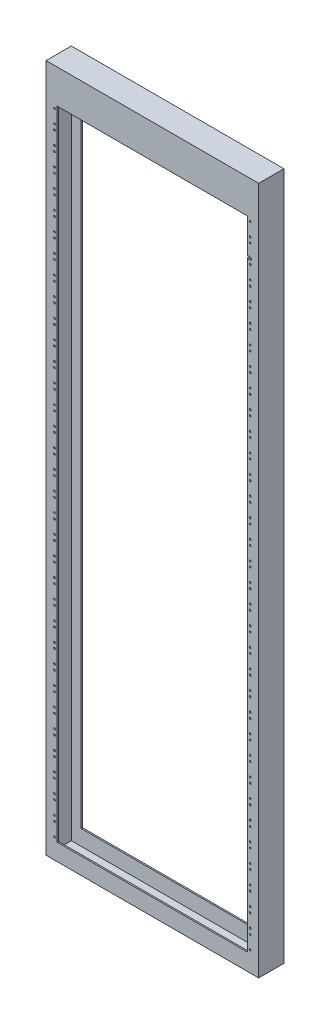
SolidWorks part; units mm, degrees
ref_plane "Front Plane" through (0, 0, 0) normal (0, 0, 1) x (1, 0, 0)
ref_plane "Top Plane" through (0, 0, 0) normal (0, 1, 0) x (1, 0, 0)
ref_plane "Right Plane" through (0, 0, 0) normal (1, 0, 0) x (0, 0, -1)
sketch "Sketch1" plane through (0, 0, 0) normal (0, 0, 1) x (1, 0, 0)
  line L0 (-26.5, -40) -> (-26.5, 1594.9)
  line L1 (0, 0) -> (452, 0)
  line L2 (0, 0) -> (0, 1514.4)
  line L3 (0, 1514.4) -> (452, 1514.4)
  line L4 (452, 0) -> (452, 1514.4)
  line L5 (-26.5, 1594.9) -> (478.5, 1594.9)
  line L6 (478.5, -40) -> (478.5, 1594.9)
  line L7 (-26.5, -40) -> (478.5, -40)
  dimension "D2" = 452
  dimension "D3" = 1634.9
  dimension "D4" = 505
  dimension "D1" = 1514.4
  dimension "D5" = 80.5
  dimension "D6" = 26.5
extrude "Boss-Extrude1" add sketch "Sketch1" along normal blind 60
shell "Shell1" thickness 3.175 removed face at (226, 1514.4, 30) removed face at (452, 757.2, 30) removed face at (226, 0, 30) removed face at (0, 757.2, 30)
hole_wizard "Tap Drill for M5x0.8 Tap1" positions "Sketch4" profile "Sketch2" hole size "M5x0.8" standard "ANSI Metric"
sketch "Sketch4" plane through (0, 0, 60) normal (0, 0, 1) x (1, 0, 0)
  line L0 (226, 1514.4) -> (226, 1594.9) construction
  line L1 (452, 1514.4) -> (0, 1514.4) construction
  line L2 (478.5, 1594.9) -> (-26.5, 1594.9) construction
  point P95 (-6.5, 1506.5)
  point P98 (-6.5, 1474.75)
  point P107 (-6.5, 1462.05)
  point P108 (-6.5, 1430.3)
  point P109 (-6.5, 1417.6)
  point P110 (-6.5, 1385.85)
  point P111 (-6.5, 1373.15)
  point P112 (-6.5, 1341.4)
  point P113 (-6.5, 1328.7)
  point P114 (-6.5, 1296.95)
  point P115 (-6.5, 1284.25)
  point P116 (-6.5, 1252.5)
  point P117 (-6.5, 1239.8)
  point P118 (-6.5, 1208.05)
  point P119 (-6.5, 1195.35)
  point P120 (-6.5, 1163.6)
  point P121 (-6.5, 1150.9)
  point P122 (-6.5, 1119.15)
  point P123 (-6.5, 1106.45)
  point P124 (-6.5, 1074.7)
  point P125 (-6.5, 1062)
  point P126 (-6.5, 1030.25)
  point P127 (-6.5, 1017.55)
  point P128 (-6.5, 985.8)
  point P129 (-6.5, 973.1)
  point P130 (-6.5, 941.35)
  point P131 (-6.5, 928.65)
  point P132 (-6.5, 896.9)
  point P133 (-6.5, 884.2)
  point P134 (-6.5, 852.45)
  point P135 (-6.5, 839.75)
  point P136 (-6.5, 808)
  point P137 (-6.5, 795.3)
  point P138 (-6.5, 763.55)
  point P139 (-6.5, 750.85)
  point P140 (-6.5, 719.1)
  point P141 (-6.5, 706.4)
  point P142 (-6.5, 674.65)
  point P143 (-6.5, 661.95)
  point P144 (-6.5, 630.2)
  point P145 (-6.5, 617.5)
  point P146 (-6.5, 585.75)
  point P147 (-6.5, 573.05)
  point P148 (-6.5, 541.3)
  point P149 (-6.5, 528.6)
  point P150 (-6.5, 496.85)
  point P151 (-6.5, 484.15)
  point P152 (-6.5, 452.4)
  point P153 (-6.5, 439.7)
  point P154 (-6.5, 407.95)
  point P155 (-6.5, 395.25)
  point P156 (-6.5, 363.5)
  point P157 (-6.5, 350.8)
  point P158 (-6.5, 319.05)
  point P159 (-6.5, 306.35)
  point P160 (-6.5, 274.6)
  point P161 (-6.5, 261.9)
  point P162 (-6.5, 230.15)
  point P163 (-6.5, 217.45)
  point P164 (-6.5, 185.7)
  point P165 (-6.5, 173)
  point P166 (-6.5, 141.25)
  point P167 (-6.5, 128.55)
  point P168 (-6.5, 96.8)
  point P169 (-6.5, 84.1)
  point P170 (-6.5, 52.35)
  point P171 (-6.5, 39.65)
  point P172 (-6.5, 7.9)
  point P173 (458.5, 7.9)
  point P174 (458.5, 39.65)
  point P175 (458.5, 52.35)
  point P176 (458.5, 84.1)
  point P177 (458.5, 96.8)
  point P178 (458.5, 128.55)
  point P179 (458.5, 141.25)
  point P180 (458.5, 173)
  point P181 (458.5, 185.7)
  point P182 (458.5, 217.45)
  point P183 (458.5, 230.15)
  point P184 (458.5, 261.9)
  point P185 (458.5, 274.6)
  point P186 (458.5, 306.35)
  point P187 (458.5, 319.05)
  point P188 (458.5, 350.8)
  point P189 (458.5, 363.5)
  point P190 (458.5, 395.25)
  point P191 (458.5, 407.95)
  point P192 (458.5, 439.7)
  point P193 (458.5, 452.4)
  point P194 (458.5, 484.15)
  point P195 (458.5, 496.85)
  point P196 (458.5, 528.6)
  point P197 (458.5, 541.3)
  point P198 (458.5, 573.05)
  point P199 (458.5, 585.75)
  point P200 (458.5, 617.5)
  point P201 (458.5, 630.2)
  point P202 (458.5, 661.95)
  point P203 (458.5, 674.65)
  point P204 (458.5, 706.4)
  point P205 (458.5, 719.1)
  point P206 (458.5, 750.85)
  point P207 (458.5, 763.55)
  point P208 (458.5, 795.3)
  point P209 (458.5, 808)
  point P210 (458.5, 839.75)
  point P211 (458.5, 852.45)
  point P212 (458.5, 884.2)
  point P213 (458.5, 896.9)
  point P214 (458.5, 928.65)
  point P215 (458.5, 941.35)
  point P216 (458.5, 973.1)
  point P217 (458.5, 985.8)
  point P218 (458.5, 1017.55)
  point P219 (458.5, 1030.25)
  point P220 (458.5, 1062)
  point P221 (458.5, 1074.7)
  point P222 (458.5, 1106.45)
  point P223 (458.5, 1119.15)
  point P224 (458.5, 1150.9)
  point P225 (458.5, 1163.6)
  point P226 (458.5, 1195.35)
  point P227 (458.5, 1208.05)
  point P228 (458.5, 1239.8)
  point P229 (458.5, 1252.5)
  point P230 (458.5, 1284.25)
  point P231 (458.5, 1296.95)
  point P232 (458.5, 1328.7)
  point P233 (458.5, 1341.4)
  point P234 (458.5, 1373.15)
  point P235 (458.5, 1385.85)
  point P236 (458.5, 1417.6)
  point P237 (458.5, 1430.3)
  point P238 (458.5, 1462.05)
  point P239 (458.5, 1474.75)
  point P240 (458.5, 1506.5)
  dimension "D1" = 232.5
  dimension "D2" = 7.9
  dimension "D3" = 31.75
  dimension "D4" = 34
sketch "Sketch2" plane through (-6.5, 1506.5, 60) normal (1, 0, 0) x (0, -1, 0)
  line L0 (0, 0) -> (0, 20.3118)
  line L1 (0, 20.3118) -> (2.1, 19.05)
  line L2 (2.1, 19.05) -> (2.1, 0)
  line L5 (2.1, 0) -> (0, 0)
  line L10 (0, 20.3118) -> (-2.1, 19.05) construction
  line L11 (0, -6.35) -> (0, 107.95) construction
  dimension "Hole Dia." = 4.2
  dimension "Hole Depth" = 19.05
  dimension "Drill Angle" = 118
hole_wizard "Tap Drill Slot for #10-24 Tap1" positions "Sketch5" profile "Sketch6" size "#10-24" standard "ANSI Inch" slot yes end condition through all
sketch "Sketch5" plane through (-317.3332, -292.8184, 88.575) normal (0, 0, 1) x (1, 0, 0)
  line L0 (768.8452, 1723.1184) -> (779.0052, 1723.1184) construction
  point P0 (773.9252, 1723.1184)
sketch "Sketch6" plane through (456.592, 1430.3, 88.575) normal (1, 0, 0) x (0, -1, 0)
  line L0 (0, 0) -> (0, 88.575)
  line L1 (0, 88.575) -> (3.175, 88.575)
  line L2 (3.175, 88.575) -> (3.175, 0)
  line L3 (3.175, 0) -> (0, 0)
  line L4 (0, -6.35) -> (0, 107.95) construction
  dimension "Thru Hole Dia." = 6.35
  dimension "Thru Hole Depth" = 88.575
